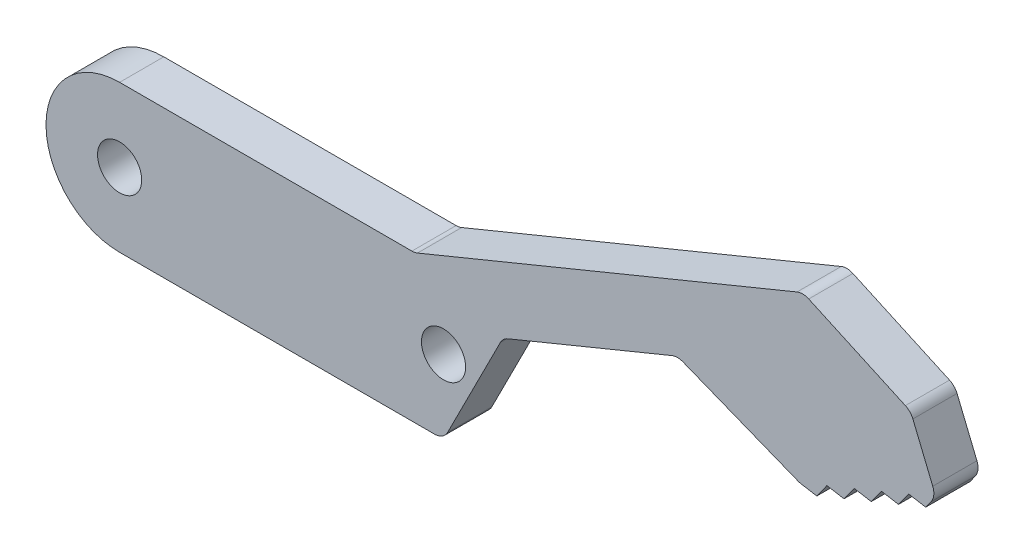
SolidWorks part; units mm, degrees
material "ABS"
ref_plane "Спереди" through (0, 0, 0) normal (0, 0, 1) x (1, 0, 0)
ref_plane "Сверху" through (0, 0, 0) normal (0, 1, 0) x (1, 0, 0)
ref_plane "Справа" through (0, 0, 0) normal (1, 0, 0) x (0, 0, -1)
sketch "Эскиз1" plane through (0, 0, 0) normal (0, 0, 1) x (1, 0, 0)
  line L0 (0, 0) -> (22, 0) construction
  line L1 (0, 5) -> (22, 5)
  line L2 (0, -5) -> (22, -5)
  line L3 (20.05, 5) -> (23.9914, -4.5863) construction
  line L4 (20.05, 5) -> (51.4959, 17.929) construction
  line L5 (23.9914, -4.5863) -> (55.4373, 8.3426) construction
  line L6 (51.4959, 17.929) -> (55.4373, 8.3426) construction
  line L7 (20.05, 5) -> (46.409, 15.8375)
  line L8 (46.409, 15.8375) -> (53.7261, 12.5046)
  line L9 (53.7261, 12.5046) -> (55.4373, 8.3426)
  line L10 (55.4373, 8.3426) -> (46.1885, 4.54)
  line L11 (46.1885, 4.54) -> (37.8854, 7.8358)
  line L12 (37.8854, 7.8358) -> (26.0289, 2.961)
  line L13 (46.1885, 4.54) -> (47.351, 4.3422)
  line L14 (47.351, 4.3422) -> (48.0382, 5.3005)
  line L15 (47.351, 4.3422) -> (54.7501, 7.3843) construction
  line L16 (48.0382, 5.3005) -> (49.2008, 5.1027)
  line L17 (49.2008, 5.1027) -> (49.888, 6.0611)
  line L18 (49.888, 6.0611) -> (51.0505, 5.8633)
  line L19 (51.0505, 5.8633) -> (51.7378, 6.8216)
  line L20 (51.7378, 6.8216) -> (52.9003, 6.6238)
  line L21 (52.9003, 6.6238) -> (53.5875, 7.5821)
  line L22 (53.5875, 7.5821) -> (54.7501, 7.3843)
  line L23 (54.7501, 7.3843) -> (55.4373, 8.3426)
  line L24 (26.0289, 2.961) -> (22, -5)
  arc A0 (0, 5) -> (0, -5) centre (0, 0) ccw
  arc A1 (22, -5) -> (22, 5) centre (22, 0) ccw
  circle A2 centre (0, 0) radius 1.5
  circle A3 centre (22, 0) radius 1.5
  point P3 (11, 0)
  dimension "D11" = 3
  dimension "D1" = 10
  dimension "D2" = 22
  dimension "D3" = 157.65
  dimension "D4" = 1.95
  dimension "D5" = 34
  dimension "D6" = 12.8195
  dimension "D7" = 10
  dimension "D8" = 4.5
  dimension "D9" = 5.5
  dimension "D10" = 136
  dimension "D12" = 2
  dimension "D13" = 0.625
  dimension "D14" = 8
extrude "Бобышка-Вытянуть2" add sketch "Эскиз1" against normal blind 3 contours L13 L14 L10 | L16 L17 L10 | L18 L19 L10 | L20 L21 L10 | L22 L23 L10 | A1 L12 L11 L10 L9 L8 L7 L1 | A1 L1 A0 L2 A3 A2 region at (10.0816, 0.1001, 0) region at (41.1721, 9.2038, 0) region at (54.5916, 7.7697, 0) region at (47.1926, 4.7276, 0) region at (52.7419, 7.0092, 0) region at (49.0423, 5.4881, 0) region at (50.8921, 6.2486, 0)
fillet "Скругление1" radius 1 8 edges at (46.1885, 4.54, -1.5) (55.4373, 8.3426, -1.5) (53.7261, 12.5046, -1.5) (46.409, 15.8375, -1.5) (20.05, 5, -1.5) (37.8854, 7.8358, -1.5) (26.0289, 2.961, -1.5) (22, -5, -1.5)
